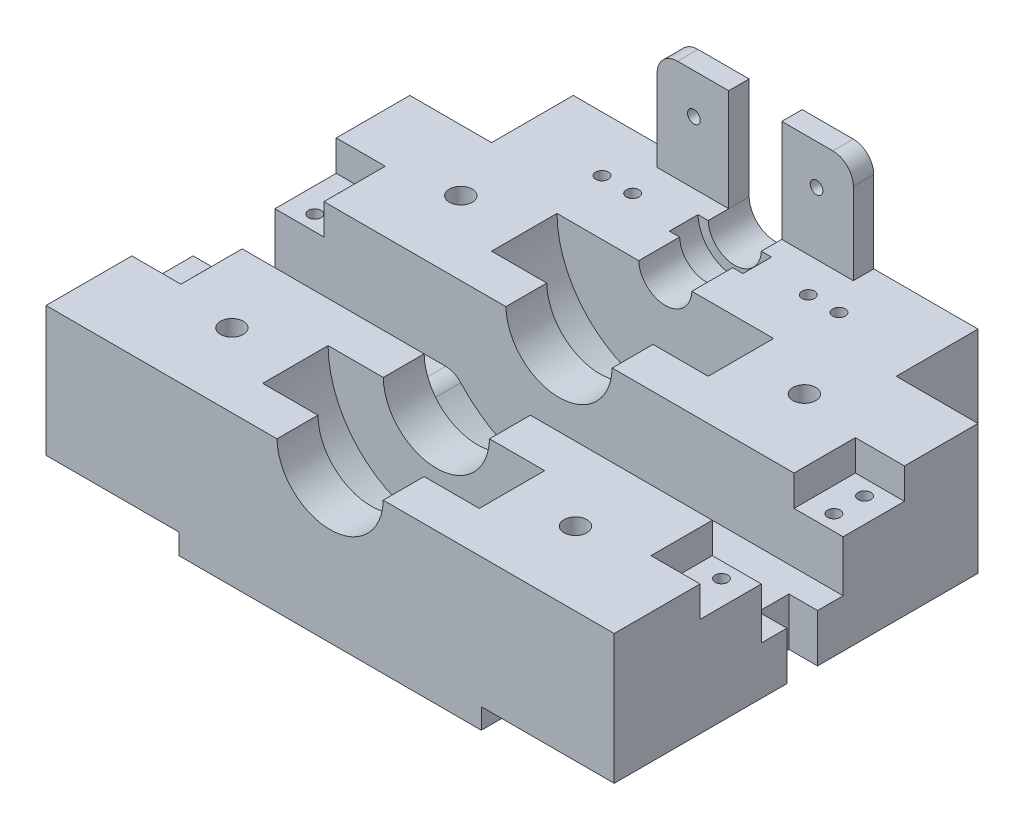
SolidWorks part; units mm, degrees
ref_plane "Front Plane" through (0, 0, 0) normal (0, 0, 1) x (1, 0, 0)
ref_plane "Top Plane" through (0, 0, 0) normal (0, 1, 0) x (1, 0, 0)
ref_plane "Right Plane" through (0, 0, 0) normal (1, 0, 0) x (0, 0, -1)
sketch "Sketch2" plane through (0, 0, 0) normal (0, 0, 1) x (1, 0, 0)
  line L5 (-57.5, 60) -> (-57.5, 50)
  line L6 (-75, -97.5) -> (75, -97.5)
  line L24 (-82.5, -90) -> (-82.5, 35)
  line L25 (-50, 67.5) -> (50, 67.5)
  line L26 (82.5, -90) -> (82.5, 35)
  line L27 (0, -100) -> (0, 100) construction
  line L28 (-100, 0) -> (100, 0) construction
  line L29 (-65, 42.5) -> (-75, 42.5)
  line L34 (57.5, 60) -> (57.5, 50)
  line L35 (65, 42.5) -> (75, 42.5)
  arc A12 (-82.5, 35) -> (-75, 42.5) centre (-75, 35) cw
  arc A19 (82.5, 35) -> (75, 42.5) centre (75, 35) ccw
  arc A20 (65, 42.5) -> (57.5, 50) centre (65, 50) cw
  arc A21 (57.5, 60) -> (50, 67.5) centre (50, 60) ccw
  arc A22 (-50, 67.5) -> (-57.5, 60) centre (-50, 60) ccw
  arc A23 (-65, 42.5) -> (-57.5, 50) centre (-65, 50) ccw
  arc A24 (-82.5, -90) -> (-75, -97.5) centre (-75, -90) ccw
  arc A25 (82.5, -90) -> (75, -97.5) centre (75, -90) cw
  circle A26 centre (52.5, -67.5) radius 12.5
  point P0 (0, 0)
  point P39 (-57.5, 67.5)
  dimension "D5" = 25
  dimension "D6" = 82.5
  dimension "D7" = 7.5
  dimension "D2" = 25
  dimension "D3" = 165
  dimension "D8" = 7.5
  dimension "D9" = 25
  dimension "D1" = 67.5
  dimension "D4" = 82.5
  dimension "D10" = 30
  dimension "D11" = 30
extrude "Boss-Extrude1" add sketch "Sketch2" against normal blind 8
sketch "Sketch3" plane through (0, 0, 0) normal (0, 0, 1) x (1, 0, 0)
  line L0 (0, 100) -> (0, -100) construction
  circle A0 centre (0, -20) radius 12.75
  dimension "D1" = 25.5
  dimension "D2" = 20
extrude "Cut-Extrude1" cut sketch "Sketch3" against normal up to surface (8 mm away) up to face at (65, -67.5, -8)
sketch "Sketch5" plane through (0, 0, -8) normal (0, 0, -1) x (-1, 0, 0)
  line L3 (-69.5, -87) -> (-69.5, -20)
  line L4 (0, 67.5) -> (0, -97.5) construction
  line L5 (-82.5, -90) -> (-82.5, 35) construction
  line L6 (-69.5, -20) -> (69.5, -20)
  line L7 (-69.5, -87) -> (69.5, -87)
  line L8 (75, -97.5) -> (-75, -97.5) construction
  line L9 (69.5, -87) -> (69.5, -20)
  line L10 (-50, 67.5) -> (50, 67.5) construction
  point P10 (0, -87)
  point P11 (0, -20)
  dimension "D1" = 10.5
  dimension "D2" = 67
  dimension "D3" = 13
extrude "Boss-Extrude2" add sketch "Sketch5" along normal blind 109
sketch "Sketch6" plane through (0, 0, -8) normal (0, 0, -1) x (-1, 0, 0)
  circle A0 centre (0, -20) radius 26.5
  circle A1 centre (0, -20) radius 12.75 construction
  dimension "D1" = 53
extrude "Cut-Extrude2" cut sketch "Sketch6" along normal blind 16 from offset 10
sketch "Sketch7" plane through (0, 0, -8) normal (0, 0, -1) x (-1, 0, 0)
  circle A0 centre (0, -20) radius 6.5
  circle A1 centre (0, -20) radius 12.75 construction
  dimension "D1" = 13
extrude "Cut-Extrude3" cut sketch "Sketch7" along normal up to surface (109 mm away) up to face at (0, -53.5, -117)
sketch "Sketch10" plane through (0, 0, -8) normal (0, 0, -1) x (-1, 0, 0)
  line L0 (-69.5, -20) -> (-69.5, -20.25)
  line L1 (-69.5, -20) -> (-69.5, -87) construction
  line L2 (-69.5, -20.25) -> (69.5, -20.25)
  line L3 (69.5, -87) -> (69.5, -20) construction
  line L4 (69.5, -20.25) -> (69.5, -20)
  line L5 (69.5, -20) -> (-69.5, -20)
  dimension "D1" = 0.25
extrude "Cut-Extrude4" cut sketch "Sketch10" along normal up to surface (109 mm away) up to face at (0, -43.4167, -117)
sketch "Sketch11" plane through (0, 0, -8) normal (0, 0, -1) x (-1, 0, 0)
  line L0 (-69.5, -72) -> (-54.5, -72)
  line L1 (-69.5, -20.25) -> (-69.5, -87) construction
  line L2 (-54.5, -72) -> (-54.5, -87)
  line L3 (-69.5, -87) -> (69.5, -87) construction
  line L4 (-69.5, -72) -> (-69.5, -87)
  line L5 (-69.5, -87) -> (-54.5, -87)
  line L11 (0, 87.7767) -> (0, -101.3295) construction
  line L12 (69.5, -87) -> (54.5, -87)
  line L13 (69.5, -72) -> (69.5, -87)
  line L14 (54.5, -72) -> (54.5, -87)
  line L15 (69.5, -72) -> (54.5, -72)
  dimension "D1" = 15
  dimension "D2" = 15
sketch "Sketch14" plane through (69.5, 0, 0) normal (1, 0, 0) x (0, 0, -1)
  line L0 (44, 4.6823) -> (44, -72.994) construction
  line L2 (64, 4.6823) -> (64, -72.994) construction
  line L3 (8, -90) -> (8, 35) construction
  line L4 (74, 4.6823) -> (74, -72.994) construction
  line L5 (90, 4.6823) -> (90, -72.994) construction
  line L6 (100, 4.6823) -> (100, -72.994) construction
  dimension "D1" = 36
  dimension "D2" = 20
  dimension "D3" = 10
  dimension "D4" = 16
  dimension "D5" = 10
sketch "Sketch15" plane through (0, 0, -8) normal (0, 0, -1) x (-1, 0, 0)
  circle A0 centre (0, -20) radius 32.5
  circle A1 centre (0, -20) radius 12.75 construction
  dimension "D1" = 65
extrude "Cut-Extrude8" cut sketch "Sketch15" along normal blind 20 from offset 36
sketch "Sketch16" plane through (69.5, 0, 0) normal (1, 0, 0) x (0, 0, -1)
  line L0 (44, -20.25) -> (44, -40.25)
  line L1 (44, 4.6823) -> (44, -72.994) construction
  line L2 (44, -40.25) -> (64, -40.25)
  line L3 (64, 4.6823) -> (64, -72.994) construction
  line L4 (64, -40.25) -> (64, -20.25)
  line L5 (64, -20.25) -> (44, -20.25)
  dimension "D1" = 20
extrude "Cut-Extrude9" cut sketch "Sketch16" against normal through all both and the other way through all
sketch "Sketch17" plane through (0, 0, -8) normal (0, 0, -1) x (-1, 0, 0)
  circle A0 centre (0, -20) radius 26.5
  circle A1 centre (0, -20) radius 12.75 construction
  dimension "D1" = 53
extrude "Cut-Extrude10" cut sketch "Sketch17" along normal blind 26 from surface starting at face at (0, -32.5625, -64)
sketch "Sketch20" plane through (0, 0, -8) normal (0, 0, -1) x (-1, 0, 0)
  line L0 (-69.5, -20.25) -> (-69.5, -87)
  line L1 (-69.5, -87) -> (69.5, -87)
  line L2 (69.5, -87) -> (69.5, -20.25)
  line L3 (69.5, -20.25) -> (-69.5, -20.25)
  line L4 (-69.5, -20.25) -> (-6.4952, -20.25) construction
  line L5 (-69.5, 4.6823) -> (-69.5, -72.994) construction
  line L6 (69.5, -87) -> (69.5, -20.25) construction
  line L7 (-69.5, -87) -> (69.5, -87) construction
extrude "Boss-Extrude6" add sketch "Sketch20" along normal blind 10 from surface starting at face at (0, -35.0625, -64)
sketch "Sketch21" plane through (0, 0, -8) normal (0, 0, -1) x (-1, 0, 0)
  circle A0 centre (0, -20) radius 13
  circle A1 centre (0, -20) radius 12.75 construction
  dimension "D1" = 26
extrude "Cut-Extrude12" cut sketch "Sketch21" along normal up to surface (66 mm away) up to face at (0, -33.375, -74)
fillet "Fillet1" radius 5 1 edges at (25.4202, -40.25, -54) type face fillet first side face at (47.4601, -40.25, -54) second side face at (0, -46.375, -54)
fillet "Fillet2" radius 5 1 edges at (-25.4202, -40.25, -54) type face fillet first side face at (-47.4601, -40.25, -54) second side face at (-0.8844, -46.7745, -54)
sketch "Sketch22" plane through (0, 0, -8) normal (0, 0, -1) x (-1, 0, 0)
  circle A0 centre (0, -20) radius 9
  circle A1 centre (0, -20) radius 12.75 construction
  dimension "D1" = 18
extrude "Cut-Extrude13" cut sketch "Sketch22" against normal blind 17 and the other way through all from surface starting at face at (0, -43.5417, -117)
sketch "Sketch23" plane through (0, 0, -117) normal (0, 0, -1) x (-1, 0, 0)
  line L0 (-8.9965, -20.25) -> (-6.4952, -20.25)
  line L1 (6.4952, -20.25) -> (8.9965, -20.25)
  arc A0 (-8.9965, -20.25) -> (8.9965, -20.25) centre (0, -20) ccw
  arc A1 (-6.4952, -20.25) -> (6.4952, -20.25) centre (0, -20) ccw
  arc A2 (-6.4952, -20.25) -> (6.4952, -20.25) centre (0, -20) ccw construction
  arc A3 (-8.9965, -20.25) -> (8.9965, -20.25) centre (0, -20) ccw construction
extrude "Boss-Extrude7" add sketch "Sketch23" against normal blind 10
sketch "Sketch24" plane through (0, 0, -117) normal (0, 0, -1) x (-1, 0, 0)
  line L0 (-69.5, -57) -> (-69.5, -87)
  line L1 (-69.5, 4.6823) -> (-69.5, -72.994) construction
  line L2 (-69.5, -87) -> (-39.5, -87)
  line L3 (-69.5, -87) -> (69.5, -87) construction
  line L4 (-39.5, -87) -> (-39.5, -57)
  line L5 (-39.5, -57) -> (-69.5, -57)
  line L6 (0, 119.6824) -> (0, -123.2201) construction
  line L7 (39.5, -57) -> (69.5, -57)
  line L8 (39.5, -87) -> (39.5, -57)
  line L9 (69.5, -87) -> (39.5, -87)
  line L10 (69.5, -57) -> (69.5, -87)
  dimension "D1" = 30
  dimension "D2" = 30
extrude "Cut-Extrude14" cut sketch "Sketch24" against normal up to surface (109 mm away) up to face at (0, -44.625, -8)
sketch "Sketch25" plane through (39.5, 0, 0) normal (1, 0, 0) x (0, 0, -1)
  line L0 (8, -57) -> (8, -87)
  line L1 (8, -87) -> (38, -87)
  line L2 (8, -87) -> (117, -87) construction
  line L3 (38, -87) -> (38, -57)
  line L4 (8, -57) -> (117, -57) construction
  line L5 (38, -57) -> (8, -57)
  line L6 (74, -57) -> (74, -87)
  line L7 (74, 4.6823) -> (74, -72.994) construction
  line L8 (74, -87) -> (117, -87)
  line L9 (117, -87) -> (117, -57)
  line L10 (117, -57) -> (74, -57)
  dimension "D1" = 30
extrude "Cut-Extrude15" cut sketch "Sketch25" against normal through all both and the other way through all
sketch "Sketch27" plane through (0, -20.25, 0) normal (0, 1, 0) x (1, 0, 0)
  point P0 (-42.0234, 82)
  point P1 (42.0234, 82)
  point P3 (-42.0234, 26)
  point P5 (42.0234, 26)
  point P7 (-28.9894, 103.5)
  point P9 (-21.4894, 103.5)
  point P11 (21.4894, 103.5)
  point P13 (28.9894, 103.5)
sketch "Sketch29" plane through (69.5, 0, 0) normal (1, 0, 0) x (0, 0, -1)
  line L0 (44, -20.25) -> (44, -27.75)
  line L1 (44, -40.25) -> (44, -20.25) construction
  line L2 (44, -27.75) -> (29, -27.75)
  line L3 (29, -27.75) -> (29, -20.25)
  line L4 (44, -20.25) -> (8, -20.25) construction
  line L5 (29, -20.25) -> (44, -20.25)
  line L6 (64, -20.25) -> (64, -27.75)
  line L7 (64, -20.25) -> (64, -40.25) construction
  line L8 (64, -27.75) -> (79, -27.75)
  line L9 (79, -27.75) -> (79, -20.25)
  line L10 (117, -20.25) -> (64, -20.25) construction
  line L11 (79, -20.25) -> (64, -20.25)
  dimension "D1" = 15
  dimension "D2" = 7.5
  dimension "D3" = 15
  dimension "D4" = 7.5
extrude "Cut-Extrude16" cut sketch "Sketch29" against normal blind 12 and the other way through all
sketch "Sketch30" plane through (-69.5, 0, 0) normal (-1, 0, 0) x (0, 0, 1)
  line L0 (-44, -20.25) -> (-29, -20.25)
  line L1 (-44, -20.25) -> (-8, -20.25) construction
  line L2 (-29, -20.25) -> (-29, -27.75)
  line L3 (-29, -27.75) -> (-44, -27.75)
  line L4 (-44, -20.25) -> (-44, -40.25) construction
  line L5 (-44, -27.75) -> (-44, -20.25)
  line L6 (-64, -27.75) -> (-79, -27.75)
  line L7 (-64, -40.25) -> (-64, -20.25) construction
  line L8 (-79, -27.75) -> (-79, -20.25)
  line L9 (-117, -20.25) -> (-64, -20.25) construction
  line L10 (-79, -20.25) -> (-64, -20.25)
  line L11 (-64, -20.25) -> (-64, -27.75)
  dimension "D1" = 15
  dimension "D2" = 15
  dimension "D3" = 7.5
extrude "Cut-Extrude17" cut sketch "Sketch30" against normal blind 12
sketch "Sketch31" plane through (-69.5, 0, 0) normal (-1, 0, 0) x (0, 0, 1)
  line L7 (-57.75, -40.25) -> (-50.25, -40.25)
  line L9 (-44, -40.25) -> (-64, -40.25) construction
  line L11 (-50.25, -40.25) -> (-50.25, -57)
  line L12 (-8, -57) -> (-117, -57) construction
  line L13 (-50.25, -57) -> (-57.75, -57)
  line L14 (-57.75, -57) -> (-57.75, -40.25)
  line L15 (-57.75, -30.25) -> (-57.75, -40.25) construction
  line L16 (-50.25, -40.25) -> (-50.25, -30.25) construction
extrude "Cut-Extrude18" cut sketch "Sketch31" against normal blind 7
sketch "Sketch32" plane through (69.5, 0, 0) normal (1, 0, 0) x (0, 0, -1)
  line L0 (50.25, -40.25) -> (57.75, -40.25)
  line L1 (57.75, -40.25) -> (57.75, -57)
  line L2 (8, -57) -> (117, -57) construction
  line L3 (57.75, -57) -> (50.25, -57)
  line L4 (50.25, -57) -> (50.25, -40.25)
  line L5 (64, -40.25) -> (44, -40.25) construction
  line L6 (50.25, -30.25) -> (50.25, -40.25) construction
  line L7 (57.75, -40.25) -> (57.75, -30.25) construction
  dimension "D1" = 7.5
extrude "Cut-Extrude19" cut sketch "Sketch32" against normal blind 7
sketch "Sketch34" plane through (0, -20.25, 0) normal (0, 1, 0) x (1, 0, 0)
  point P0 (-63.5, 75.25)
  point P1 (-63.5, 67.75)
  point P3 (-63.5, 40.25)
  point P5 (-63.5, 32.75)
  point P7 (63.5, 75.25)
  point P9 (63.5, 67.75)
  point P11 (63.5, 40.25)
  point P13 (63.5, 32.75)
  point P15 (28.9894, 103.5)
  point P17 (21.4894, 103.5)
  point P19 (-28.9894, 103.5)
  point P21 (-21.4894, 103.5)
hole_wizard "Ø1.0mm Dowel Hole2" positions "Sketch34" profile "Sketch35" hole size "Ø1.0" standard "ANSI Metric"
sketch "Sketch35" plane through (-63.5, -20.25, -75.25) normal (1, 0, 0) x (0, 0, 1)
  line L0 (0, 0) -> (0, 25.9313)
  line L1 (0, 25.9313) -> (1.55, 25)
  line L2 (1.55, 25) -> (1.55, 0)
  line L5 (1.55, 0) -> (0, 0)
  line L10 (0, 25.9313) -> (-1.55, 25) construction
  line L11 (0, -6.35) -> (0, 107.95) construction
  dimension "Hole Dia." = 3.1
  dimension "Hole Depth" = 25
  dimension "Drill Angle" = 118
sketch "Sketch36" plane through (0, -20.25, 0) normal (0, 1, 0) x (1, 0, 0)
  point P0 (-42.0234, 82)
  point P3 (-42.0234, 26)
  point P6 (42.0234, 26)
  point P9 (42.0234, 82)
hole_wizard "Ø1.0mm Dowel Hole3" positions "Sketch36" profile "Sketch37" hole size "Ø1.0" standard "ANSI Metric"
sketch "Sketch37" plane through (-42.0234, -20.25, -82) normal (1, 0, 0) x (0, 0, 1)
  line L0 (0, 0) -> (0, 26.6824)
  line L1 (0, 26.6824) -> (2.8, 25)
  line L2 (2.8, 25) -> (2.8, 0)
  line L5 (2.8, 0) -> (0, 0)
  line L10 (0, 26.6824) -> (-2.8, 25) construction
  line L11 (0, -6.35) -> (0, 107.95) construction
  dimension "Hole Dia." = 5.6
  dimension "Hole Depth" = 25
  dimension "Drill Angle" = 118
sketch "Sketch38" plane through (0, -20.25, 0) normal (0, 1, 0) x (1, 0, 0)
  line L0 (49.5, 117) -> (49.5, 97)
  line L1 (69.5, 117) -> (6.4952, 117) construction
  line L2 (49.5, 97) -> (69.5, 97)
  line L3 (69.5, 117) -> (69.5, 79) construction
  line L4 (69.5, 97) -> (69.5, 117)
  line L5 (69.5, 117) -> (49.5, 117)
  line L6 (-69.5, 117) -> (-49.5, 117)
  line L7 (-6.4952, 117) -> (-69.5, 117) construction
  line L8 (-49.5, 117) -> (-49.5, 97)
  line L10 (-49.5, 97) -> (-69.5, 97)
  line L11 (-69.5, 117) -> (-69.5, 79) construction
  line L12 (-69.5, 97) -> (-69.5, 117)
  dimension "D1" = 20
  dimension "D2" = 20
  dimension "D3" = 20
  dimension "D4" = 20
extrude "Cut-Extrude20" cut sketch "Sketch38" against normal through all
fillet "Fillet3" radius 2 1 edges at (62.5, -57, -54) type face fillet first side face at (62.5, -48.625, -54) second side face at (0, -57, -56)
fillet "Fillet4" radius 2 1 edges at (-62.5, -57, -54) type face fillet first side face at (-62.5, -48.625, -54) second side face at (0, -57, -56)
sketch "Sketch39" plane through (0, 0, -74) normal (0, 0, -1) x (-1, 0, 0)
  line L0 (-39.5, -81.5) -> (-39.5, -87)
  line L1 (-39.5, -87) -> (-39.5, -57) construction
  line L2 (-39.5, -87) -> (39.5, -87)
  line L3 (39.5, -87) -> (39.5, -81.5)
  line L4 (39.5, -57) -> (39.5, -87) construction
  line L5 (39.5, -81.5) -> (-39.5, -81.5)
  line L6 (72.5, -82.5) -> (-72.5, -82.5) construction
  dimension "D1" = 1
extrude "Cut-Extrude21" cut sketch "Sketch39" against normal up to surface (36 mm away) up to face at (0, -72, -38)
sketch "Sketch41" plane through (0, 0, 0) normal (0, 0, 1) x (1, 0, 0)
  point P0 (-75, 35)
  point P3 (-50, 35)
  point P6 (-50, 60)
  point P9 (-25, 60)
  point P12 (0, 60)
  point P15 (25, 60)
  point P18 (50, 60)
  point P21 (50, 35)
  point P24 (75, 35)
  point P28 (-75, -90)
  point P31 (-50, -90)
  point P34 (-25, -90)
  point P37 (0, -90)
  point P40 (25, -90)
  point P43 (50, -90)
  point P46 (75, -90)
hole_wizard "CBORE for M4 SHCS1" positions "Sketch41" profile "Sketch42" counterbore size "M4" standard "ANSI Metric" end condition through all
sketch "Sketch42" plane through (-75, 35, 0) normal (1, 0, 0) x (0, -1, 0)
  line L0 (0, 0) -> (0, 117)
  line L1 (0, 117) -> (2.25, 117)
  line L3 (2.25, 117) -> (2.25, 4)
  line L4 (2.25, 4) -> (4, 4)
  line L5 (4, 4) -> (4, 0)
  line L7 (4, 0) -> (0, 0)
  line L11 (0, -6.35) -> (0, 107.95) construction
  dimension "Thru Hole Dia." = 4.5
  dimension "Thru Hole Depth" = 117
  dimension "C'Bore Dia." = 8
  dimension "C'Bore Depth" = 4
sketch "Sketch43" plane through (0, 0, 0) normal (0, 0, 1) x (1, 0, 0)
  line L0 (-35, 52.5) -> (35, 52.5)
  line L1 (35, 52.5) -> (35, 12.5)
  line L2 (35, 12.5) -> (-35, 12.5)
  line L3 (-35, 12.5) -> (-35, 52.5)
  line L4 (50, 67.5) -> (-50, 67.5) construction
  line L6 (82.5, -90) -> (82.5, 35) construction
  dimension "D1" = 15
  dimension "D2" = 70
  dimension "D3" = 47.5
  dimension "D4" = 40
extrude "Cut-Extrude22" cut sketch "Sketch43" against normal through all both and the other way through all
sketch "Sketch44" plane through (0, 0, -117) normal (0, 0, -1) x (-1, 0, 0)
  line L0 (-69.5, -57) -> (-39.5, -57)
  line L1 (-49.5, -57) -> (-69.5, -57) construction
  line L2 (-39.5, -81.5) -> (-39.5, -57) construction
  line L5 (-69.5, -57) -> (-69.5, -20.25) construction
  line L6 (-69.5, -52) -> (-69.5, -57)
  line L7 (39.5, -57) -> (69.5, -57)
  line L8 (49.5, -57) -> (-49.5, -57) construction
  line L9 (69.5, -57) -> (49.5, -57) construction
  line L10 (69.5, -57) -> (69.5, -52)
  line L11 (69.5, -57) -> (69.5, -20.25) construction
  line L14 (-39.5, -57) -> (-39.5, -81.5)
  line L15 (39.5, -81.5) -> (-39.5, -81.5) construction
  line L16 (-39.5, -81.5) -> (-37, -81.5)
  line L17 (-37, -81.5) -> (-37, -52)
  line L19 (39.5, -57) -> (39.5, -81.5)
  line L20 (39.5, -57) -> (39.5, -81.5) construction
  line L21 (39.5, -81.5) -> (37, -81.5)
  line L22 (37, -81.5) -> (37, -52)
  line L24 (-69.5, -52) -> (-37, -52)
  line L25 (37, -52) -> (69.5, -52)
  dimension "D1" = 5
  dimension "D2" = 5
  dimension "D3" = 2.5
  dimension "D4" = 2.5
extrude "Cut-Extrude23" cut sketch "Sketch44" against normal up to surface (109 mm away) up to face at (0, 32.5, -8)
sketch "Sketch46" plane through (0, -20.25, 0) normal (0, 1, 0) x (1, 0, 0)
  line L0 (-6.4952, 117) -> (-6.4952, 112)
  line L1 (-6.4952, 117) -> (-49.5, 117) construction
  line L2 (-6.4952, 107) -> (-6.4952, 117) construction
  line L3 (-6.4952, 112) -> (-23.9952, 112)
  line L4 (-23.9952, 112) -> (-23.9952, 117)
  line L5 (-23.9952, 117) -> (-6.4952, 117)
  line L6 (6.4952, 117) -> (6.4952, 112)
  line L7 (6.4952, 107) -> (6.4952, 117) construction
  line L8 (49.5, 117) -> (6.4952, 117) construction
  line L9 (6.4952, 112) -> (23.9952, 112)
  line L10 (23.9952, 112) -> (23.9952, 117)
  line L11 (23.9952, 117) -> (6.4952, 117)
  dimension "D1" = 5
  dimension "D2" = 17.5
extrude "Boss-Extrude8" add sketch "Sketch46" along normal blind 25
sketch "Sketch47" plane through (0, 0, -117) normal (0, 0, -1) x (-1, 0, 0)
  line L0 (0, -20) -> (14.967, -20) construction
  line L1 (0, -20) -> (0, -34.967) construction
  circle A0 centre (0, -20) radius 12.75 construction
  circle A1 centre (-15, -5) radius 1.55
  circle A2 centre (15, -5) radius 1.55
  circle A3 centre (15, -35) radius 1.55
  circle A4 centre (-15, -35) radius 1.55
  point P2 (15, -5)
  point P4 (15, -35)
  point P5 (-15, -35)
  point P10 (-15, -5)
  dimension "D9" = 3.1
  dimension "D1" = 15
  dimension "D2" = 15
  dimension "D3" = 15
  dimension "D4" = 15
  dimension "D5" = 15
  dimension "D6" = 15
  dimension "D7" = 15
  dimension "D8" = 15
fillet "Fillet5" radius 5 1 edges at (23.9952, 4.75, -114.5) type face fillet first side face at (23.9952, -7.75, -114.5) second side face at (15.2452, 4.75, -114.5)
fillet "Fillet6" radius 5 1 edges at (-23.9952, 4.75, -114.5) type face fillet first side face at (-15.2452, 4.75, -114.5) second side face at (-23.9952, -7.75, -114.5)
extrude "Cut-Extrude24" cut sketch "Sketch47" against normal blind 10
sketch "Sketch48" plane through (82.5, 0, 0) normal (1, 0, 0) x (0, 0, -1)
  line L0 (0, 67.5) -> (0, -97.5)
  line L1 (0, -97.5) -> (8, -97.5)
  line L2 (8, -97.5) -> (8, 67.5)
  line L3 (8, 67.5) -> (0, 67.5)
  line L4 (8, -90) -> (8, 35) construction
  line L5 (8, 67.5) -> (0, 67.5) construction
  line L6 (8, -97.5) -> (0, -97.5) construction
extrude "Cut-Extrude25" cut sketch "Sketch48" against normal through all both and the other way through all
